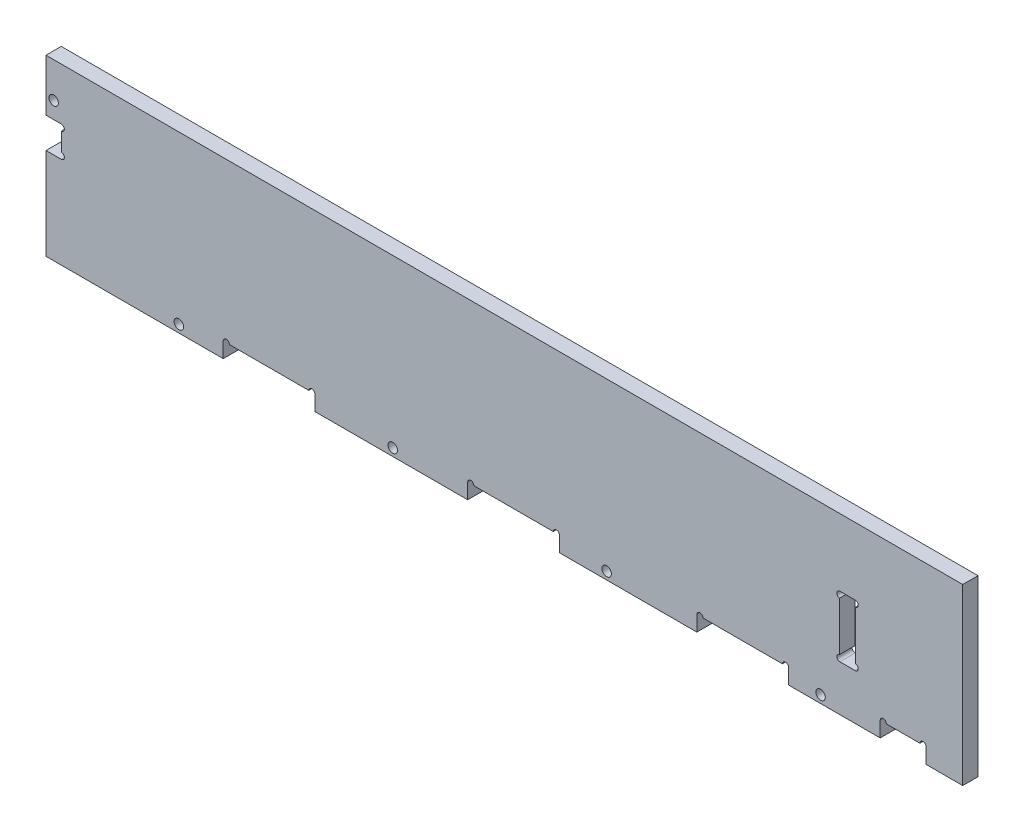
SolidWorks part; units mm, degrees
material "사용자정의 플라스틱"
ref_plane "정면" through (0, 0, 0) normal (0, 0, 1) x (1, 0, 0)
ref_plane "윗면" through (0, 0, 0) normal (0, 1, 0) x (1, 0, 0)
ref_plane "우측면" through (0, 0, 0) normal (1, 0, 0) x (0, 0, -1)
sketch "스케치1" plane through (0, 0, 0) normal (0, 0, 1) x (1, 0, 0)
  line L1 (0, 0) -> (300, 0)
  line L2 (0, 0) -> (0, 57)
  line L3 (0, 57) -> (300, 57)
  line L4 (300, 0) -> (300, 57)
  dimension "D1" = 57
  dimension "D2" = 300
extrude "보스-돌출1" add sketch "스케치1" along normal blind 5
sketch "스케치2" plane through (0, 0, 5) normal (0, 0, 1) x (1, 0, 0)
  line L0 (0, 57) -> (0, 0) construction
  line L1 (5, 40) -> (0, 40)
  line L2 (5, 40) -> (5, 30)
  line L3 (5, 30) -> (0, 30)
  line L4 (0, 40) -> (0, 30)
  line L5 (5, 30) -> (0, 30) construction
  line L6 (0, 0) -> (300, 0) construction
  line L7 (58, 5) -> (88, 5)
  line L8 (58, 5) -> (58, 0)
  line L9 (58, 0) -> (88, 0)
  line L10 (88, 5) -> (88, 0)
  line L11 (88, 5) -> (88, 0) construction
  line L12 (168, 5) -> (168, 0) construction
  line L13 (168, 0) -> (138, 0)
  line L14 (168, 0) -> (168, 5)
  line L15 (168, 5) -> (138, 5)
  line L16 (138, 0) -> (138, 5)
  line L17 (243, 5) -> (243, 0) construction
  line L18 (243, 0) -> (213, 0)
  line L19 (243, 0) -> (243, 5)
  line L20 (243, 5) -> (213, 5)
  line L21 (213, 0) -> (213, 5)
  line L22 (288, 5) -> (288, 0) construction
  line L23 (288, 0) -> (273, 0)
  line L24 (288, 0) -> (288, 5)
  line L25 (288, 5) -> (273, 5)
  line L26 (273, 0) -> (273, 5)
  line L28 (259.8, 35) -> (264.8, 35)
  line L29 (259.8, 35) -> (259.8, 15)
  line L30 (259.8, 15) -> (264.8, 15)
  line L31 (264.8, 35) -> (264.8, 15)
extrude "컷-돌출1" cut sketch "스케치2" against normal blind 5
sketch "스케치3" plane through (0, 0, 5) normal (0, 0, 1) x (1, 0, 0)
  line L0 (264.8, 35) -> (259.8, 35) construction
  line L1 (259.8, 15) -> (264.8, 15) construction
  line L2 (264.8, 15) -> (264.8, 35) construction
  line L3 (259.8, 35) -> (259.8, 15) construction
  line L4 (243, 5) -> (213, 5) construction
  line L5 (88, 5) -> (58, 5) construction
  line L6 (168, 5) -> (138, 5) construction
  line L7 (5, 30) -> (5, 40) construction
  line L8 (288, 5) -> (273, 5) construction
  line L9 (273, 5) -> (273, 0) construction
  line L10 (288, 0) -> (288, 5) construction
  circle A0 centre (274, 5) radius 1
  circle A1 centre (287, 5) radius 1
  circle A2 centre (259.8, 16) radius 1
  circle A3 centre (264.8, 16) radius 1
  circle A4 centre (264.8, 34) radius 1
  circle A5 centre (259.8, 34) radius 1
  circle A6 centre (214, 5) radius 1
  circle A7 centre (242, 5) radius 1
  circle A8 centre (87, 5) radius 1
  circle A9 centre (139, 5) radius 1
  circle A10 centre (167, 5) radius 1
  circle A11 centre (5, 31) radius 1
  circle A12 centre (5, 39) radius 1
  circle A13 centre (59, 5) radius 1
  dimension "D1" = 2
  dimension "D2" = 2
extrude "컷-돌출2" cut sketch "스케치3" against normal blind 5
sketch "스케치4" plane through (0, 0, 0) normal (0, 0, -1) x (-1, 0, 0)
  line L0 (-45.0287, 2.5) -> (-41.9287, 2.5) construction
  line L1 (-2.5, 43.9) -> (-2.5, 47) construction
  line L2 (-5, 43.9) -> (0, 43.9) construction
  line L3 (-45.0287, 5) -> (-45.0287, 0) construction
  line L4 (-5, 47) -> (0, 47) construction
  line L6 (-41.9287, 5) -> (-41.9287, 0) construction
  line L9 (-115.0287, 2.5) -> (-111.9287, 2.5) construction
  line L10 (-115.0287, 5) -> (-115.0287, 0) construction
  line L11 (-111.9287, 5) -> (-111.9287, 0) construction
  line L12 (-185.0287, 2.5) -> (-181.9287, 2.5) construction
  line L13 (-185.0287, 5) -> (-185.0287, 0) construction
  line L14 (-181.9287, 5) -> (-181.9287, 0) construction
  line L15 (-255.0287, 2.5) -> (-251.9287, 2.5) construction
  line L16 (-255.0287, 5) -> (-255.0287, 0) construction
  line L17 (-251.9287, 5) -> (-251.9287, 0) construction
  circle A0 centre (-253.4787, 2.5) radius 1.55
  circle A1 centre (-183.4787, 2.5) radius 1.55
  circle A2 centre (-113.4787, 2.5) radius 1.55
  circle A3 centre (-43.4787, 2.5) radius 1.55
  circle A4 centre (-2.5, 45.45) radius 1.55
extrude "컷-돌출3" cut sketch "스케치4" against normal blind 10
sketch "스케치5" plane through (0, 0, 5) normal (0, 0, 1) x (1, 0, 0)
  line L0 (43.45, 57) -> (43.45, 49)
  line L1 (46.55, 45) -> (43.45, 45) construction
  line L2 (47.75, 49) -> (47.75, 46.2) construction
  line L3 (43.45, 49) -> (43.45, 46.2) construction
  line L4 (46.55, 57) -> (43.45, 57)
  line L5 (47.75, 46.2) -> (46.55, 46.2)
  line L6 (46.55, 57) -> (46.55, 49)
  line L7 (42.25, 46.2) -> (42.25, 49) construction
  line L8 (46.55, 49) -> (47.75, 49)
  line L9 (46.55, 46.2) -> (46.55, 49) construction
  line L10 (43.45, 46.2) -> (43.45, 45)
  line L11 (46.55, 49) -> (43.45, 49) construction
  line L12 (46.55, 46.2) -> (43.45, 46.2) construction
  line L13 (43.45, 46.2) -> (42.25, 46.2)
  line L14 (46.55, 46.2) -> (46.55, 45)
  line L15 (45, 45) -> (45, 43.45) construction
  line L16 (42.25, 49) -> (43.45, 49)
  line L17 (47.75, 47.6) -> (46.55, 47.6) construction
  line L18 (42.25, 47.6) -> (43.45, 47.6) construction
  line L19 (45, 46.2) -> (45, 45) construction
  line L20 (42.25, 47.6) -> (40.85, 47.6) construction
  line L21 (47.75, 47.6) -> (49.15, 47.6) construction
  line L22 (0, 57) -> (45, 57) construction
  line L23 (300, 57) -> (0, 57) construction
  line L24 (45, 57) -> (150, 57) construction
  line L25 (150, 57) -> (255, 57) construction
  line L26 (255, 57) -> (300, 57) construction
  line L49 (151.55, 49) -> (152.75, 49)
  line L50 (151.55, 49) -> (148.45, 49) construction
  line L51 (148.45, 46.2) -> (148.45, 45)
  line L52 (147.25, 46.2) -> (147.25, 49) construction
  line L53 (148.45, 57) -> (148.45, 49)
  line L54 (151.55, 57) -> (151.55, 49)
  line L55 (151.55, 46.2) -> (151.55, 45)
  line L56 (150, 46.2) -> (150, 45) construction
  line L57 (151.55, 46.2) -> (151.55, 49) construction
  line L58 (152.75, 47.6) -> (154.15, 47.6) construction
  line L59 (152.75, 46.2) -> (151.55, 46.2)
  line L60 (148.45, 49) -> (148.45, 46.2) construction
  line L61 (147.25, 47.6) -> (145.85, 47.6) construction
  line L62 (151.55, 57) -> (148.45, 57)
  line L63 (148.45, 46.2) -> (147.25, 46.2)
  line L64 (151.55, 46.2) -> (148.45, 46.2) construction
  line L65 (151.55, 45) -> (148.45, 45) construction
  line L66 (147.25, 47.6) -> (148.45, 47.6) construction
  line L67 (147.25, 49) -> (148.45, 49)
  line L68 (152.75, 49) -> (152.75, 46.2) construction
  line L69 (150, 45) -> (150, 43.45) construction
  line L70 (152.75, 47.6) -> (151.55, 47.6) construction
  line L71 (256.55, 49) -> (257.75, 49)
  line L72 (256.55, 49) -> (253.45, 49) construction
  line L73 (253.45, 46.2) -> (253.45, 45)
  line L74 (252.25, 46.2) -> (252.25, 49) construction
  line L75 (253.45, 57) -> (253.45, 49)
  line L76 (256.55, 57) -> (256.55, 49)
  line L77 (256.55, 46.2) -> (256.55, 45)
  line L78 (255, 46.2) -> (255, 45) construction
  line L79 (256.55, 46.2) -> (256.55, 49) construction
  line L80 (257.75, 47.6) -> (259.15, 47.6) construction
  line L81 (257.75, 46.2) -> (256.55, 46.2)
  line L82 (253.45, 49) -> (253.45, 46.2) construction
  line L83 (252.25, 47.6) -> (250.85, 47.6) construction
  line L84 (256.55, 57) -> (253.45, 57)
  line L85 (253.45, 46.2) -> (252.25, 46.2)
  line L86 (256.55, 46.2) -> (253.45, 46.2) construction
  line L87 (256.55, 45) -> (253.45, 45) construction
  line L88 (252.25, 47.6) -> (253.45, 47.6) construction
  line L89 (252.25, 49) -> (253.45, 49)
  line L90 (257.75, 49) -> (257.75, 46.2) construction
  line L91 (255, 45) -> (255, 43.45) construction
  line L92 (257.75, 47.6) -> (256.55, 47.6) construction
  arc A0 (43.45, 45) -> (46.55, 45) centre (45, 45) ccw
  arc A1 (47.75, 46.2) -> (47.75, 49) centre (47.75, 47.6) ccw
  arc A2 (42.25, 49) -> (42.25, 46.2) centre (42.25, 47.6) ccw
  arc A6 (152.75, 46.2) -> (152.75, 49) centre (152.75, 47.6) ccw
  arc A7 (147.25, 49) -> (147.25, 46.2) centre (147.25, 47.6) ccw
  arc A8 (148.45, 45) -> (151.55, 45) centre (150, 45) ccw
  arc A9 (257.75, 46.2) -> (257.75, 49) centre (257.75, 47.6) ccw
  arc A10 (252.25, 49) -> (252.25, 46.2) centre (252.25, 47.6) ccw
  arc A11 (253.45, 45) -> (256.55, 45) centre (255, 45) ccw
  dimension "D1" = 3.1
  dimension "D2" = 5.5
  dimension "D3" = 2.8
  dimension "D4" = 1.2
  dimension "D5" = 8
  dimension "D6" = 3.1
  dimension "D7" = 45
  dimension "D14" = 3.1
  dimension "D15" = 5.5
  dimension "D16" = 2.8
  dimension "D17" = 1.2
  dimension "D18" = 8
  dimension "D19" = 3.1
  dimension "D20" = 3.1
  dimension "D21" = 5.5
  dimension "D22" = 2.8
  dimension "D23" = 1.2
  dimension "D24" = 8
  dimension "D25" = 3.1
extrude "컷-돌출4" [suppressed] cut sketch "스케치5" against normal blind 10
sketch "스케치7" plane through (0, 0, 5) normal (0, 0, 1) x (1, 0, 0)
  line L0 (259.8, 33) -> (259.8, 17) construction
  line L1 (259.7, 33.9113) -> (264.9, 33.9113)
  line L2 (259.7, 33.9113) -> (259.7, 16.1106)
  line L3 (259.7, 16.1106) -> (264.9, 16.1106)
  line L4 (264.9, 33.9113) -> (264.9, 16.1106)
  line L5 (264.8, 17) -> (264.8, 33) construction
  dimension "D1" = 0.1
  dimension "D2" = 0.1
extrude "컷-돌출5" cut sketch "스케치7" against normal blind 10
